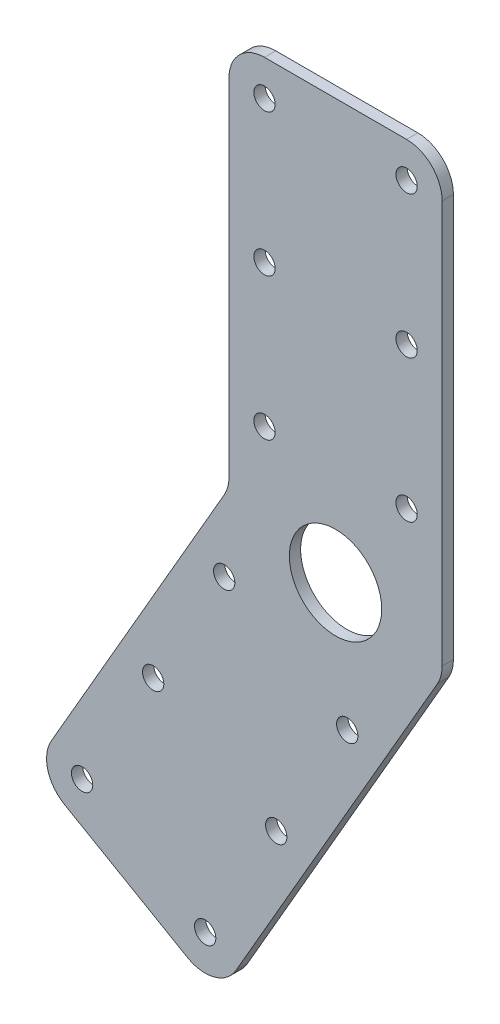
SolidWorks part; units mm, degrees
material "6061 Alloy"
ref_plane "Front Plane" through (0, 0, 0) normal (0, 0, 1) x (1, 0, 0)
ref_plane "Top Plane" through (0, 0, 0) normal (0, 1, 0) x (1, 0, 0)
ref_plane "Right Plane" through (0, 0, 0) normal (1, 0, 0) x (0, 0, -1)
sketch "Sketch1" plane through (0, 0, 0) normal (0, 0, 1) x (1, 0, 0)
  line L0 (0, 0) -> (0, 55)
  line L1 (0, 55) -> (30, 55)
  line L2 (30, 55) -> (30, -8.0385)
  line L3 (30, -8.0385) -> (-1.5192, -62.6314)
  line L4 (-1.5192, -62.6314) -> (-27.5, -47.6314)
  line L5 (-27.5, -47.6314) -> (0, 0)
  line L6 (0, 0) -> (30, -8.0385) construction
  line L7 (5, 55) -> (5, 0) construction
  line L8 (0, 0) -> (5, 0) construction
  line L9 (5, 50) -> (5, 55) construction
  line L10 (15, 55) -> (15, -4.0192) construction
  line L11 (-23.1699, -50.1314) -> (4.3301, -2.5) construction
  line L12 (0, 0) -> (4.3301, -2.5) construction
  line L13 (0, 27.5) -> (5, 30) construction
  line L15 (-14.5096, -55.1314) -> (15, -4.0192) construction
  line L16 (15, -4.0192) -> (7.9904, -16.1603) construction
  line L17 (7.9904, -16.1603) -> (16.6506, -21.1603) construction
  circle A0 centre (15, -4.0192) radius 6.5
  circle A1 centre (5, 50) radius 1.5
  circle A2 centre (5, 30) radius 1.5
  circle A3 centre (5, 10) radius 1.5
  circle A4 centre (25, 10) radius 1.5
  circle A5 centre (25, 30) radius 1.5
  circle A6 centre (25, 50) radius 1.5
  circle A7 centre (-20.6699, -45.8013) radius 1.5
  circle A8 centre (-10.6699, -28.4808) radius 1.5
  circle A9 centre (-0.6699, -11.1603) radius 1.5
  circle A10 centre (16.6506, -21.1603) radius 1.5
  circle A11 centre (6.6506, -38.4808) radius 1.5
  circle A12 centre (-3.3494, -55.8013) radius 1.5
  dimension "D5" = 13
  dimension "D7" = 3
  dimension "D9" = 20
  dimension "D10" = 20
  dimension "D11" = 5
  dimension "D1" = 30
  dimension "D2" = 55
  dimension "D3" = 55
  dimension "D4" = 150
  dimension "D6" = 5
  dimension "D8" = 5
  dimension "D12" = 20
  dimension "D13" = 20
extrude "Boss-Extrude1" add sketch "Sketch1" along normal blind 1.5875
fillet "Fillet1" radius 5 6 edges at (30, -8.0385, 0.7937) (0, 0, 0.7937) (-1.5192, -62.6314, 0.7937) (-27.5, -47.6314, 0.7937) (0, 55, 0.7937) (30, 55, 0.7937)
